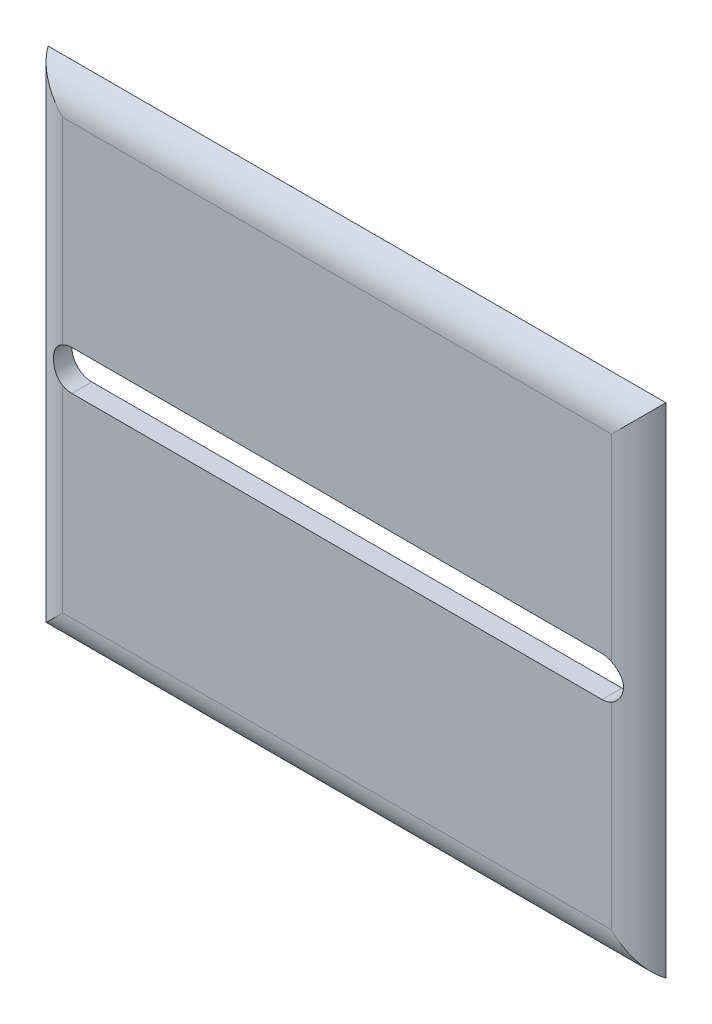
SolidWorks part; units mm, degrees
ref_plane "前视基准面" through (0, 0, 0) normal (0, 0, 1) x (1, 0, 0)
ref_plane "上视基准面" through (0, 0, 0) normal (0, 1, 0) x (1, 0, 0)
ref_plane "右视基准面" through (0, 0, 0) normal (1, 0, 0) x (0, 0, -1)
sketch "草图1" plane through (0, 0, 0) normal (0, 0, 1) x (1, 0, 0)
  line L0 (11, 62.5) -> (144, 62.5) construction
  line L1 (0, 0) -> (155, 0)
  line L2 (0, 0) -> (0, 125)
  line L3 (0, 125) -> (155, 125)
  line L4 (155, 0) -> (155, 125)
  line L5 (0, 0) -> (155, 125) construction
  line L6 (0, 125) -> (155, 0) construction
  line L7 (11, 67.5) -> (144, 67.5)
  line L8 (11, 57.5) -> (144, 57.5)
  arc A0 (11, 67.5) -> (11, 57.5) centre (11, 62.5) ccw
  arc A1 (144, 57.5) -> (144, 67.5) centre (144, 62.5) ccw
  point P4 (77.5, 62.5)
  point P8 (77.5, 62.5)
  point P13 (6, 62.5)
  point P15 (155, 62.5)
  dimension "D4" = 11
  dimension "D1" = 155
  dimension "D2" = 125
  dimension "D3" = 6
  dimension "D5" = 5
extrude "凸台-拉伸1" add sketch "草图1" along normal blind 5
fillet "圆角1" radius 10 4 edges at (0, 62.5, 5) (77.5, 0, 5) (155, 62.5, 5) (77.5, 125, 5)
